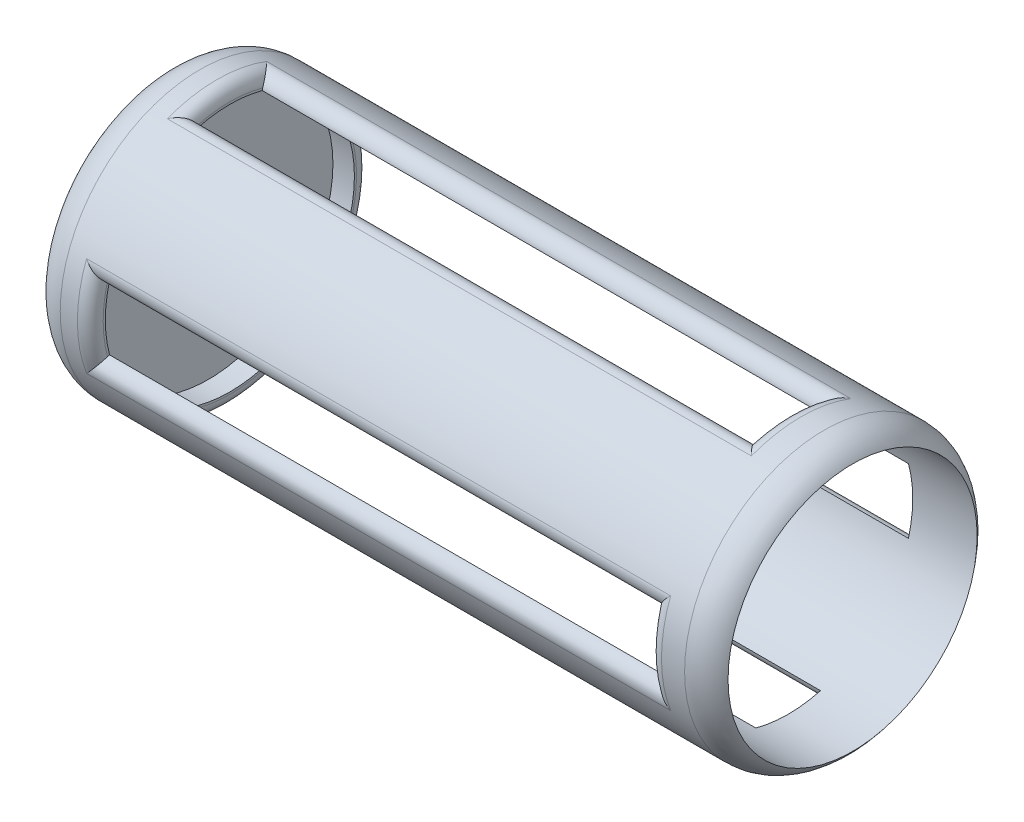
SolidWorks part; units mm, degrees
ref_plane "Front Plane" through (0, 0, 0) normal (0, 0, 1) x (1, 0, 0)
ref_plane "Top Plane" through (0, 0, 0) normal (0, 1, 0) x (1, 0, 0)
ref_plane "Right Plane" through (0, 0, 0) normal (1, 0, 0) x (0, 0, -1)
sketch "Sketch2" plane through (0, 0, 0) normal (1, 0, 0) x (0, 0, -1)
  circle A0 centre (0, 0) radius 32.5
  dimension "D1" = 65
extrude "Boss-Extrude1" add sketch "Sketch2" along normal blind 160
sketch "Sketch3" plane through (160, 0, 0) normal (1, 0, 0) x (0, 0, -1)
  circle A2 centre (0, 0) radius 29.0411
sketch "Sketch4" plane through (0, 0, 0) normal (0, 0, 1) x (1, 0, 0)
  line L0 (0, 32.5) -> (0, -32.5) construction
  line L1 (160, -32.5) -> (160, 32.5) construction
  line L3 (15, 7.5) -> (145, 7.5)
  line L4 (15, 7.5) -> (15, -7.5)
  line L5 (15, -7.5) -> (145, -7.5)
  line L6 (145, 7.5) -> (145, -7.5)
  point P5 (85, 0)
  dimension "D1" = 15
  dimension "D2" = 130
  dimension "D3" = 15
  dimension "D4" = 15
  dimension "D5" = 15
  dimension "D6" = 130
extrude "Cut-Extrude2" cut sketch "Sketch4" against normal blind 50 and the other way blind 50
sketch "Sketch5" plane through (0, 0, 0) normal (0, 1, 0) x (1, 0, 0)
  line L3 (15, 7.5) -> (145, 7.5)
  line L4 (15, 7.5) -> (15, -7.5)
  line L5 (15, -7.5) -> (145, -7.5)
  line L6 (145, 7.5) -> (145, -7.5)
  point P5 (85, 0)
  dimension "D1" = 130
extrude "Cut-Extrude3" cut sketch "Sketch5" against normal blind 50 and the other way blind 50
fillet "Fillet2" radius 3 16 edges at (80, 7.5, 31.6228) (80, -7.5, 31.6228) (80, -31.6228, 7.5) (80, -31.6228, -7.5) (80, -7.5, -31.6228) (80, 7.5, -31.6228) (80, 31.6228, -7.5) (80, 31.6228, 7.5) (145, 0, 32.5) (15, 0, 32.5) (145, 0, -32.5) (15, 0, -32.5) (15, 32.5, 0) (145, 32.5, 0) (15, -32.5, 0) (145, -32.5, 0) tangent propagation no
ref_plane "Plane1" through (170, 0, 0) normal (1, 0, 0) x (0, 0, -1)
sketch "Sketch6" plane through (170, 0, 0) normal (1, 0, 0) x (0, 0, -1)
  circle A0 centre (0, 0) radius 29
extrude "Cut-Extrude4" cut sketch "Sketch6" against normal blind 160
fillet "Fillet3" radius 8 2 edges at (160, 0, -32.5) (0, 0, -32.5)
